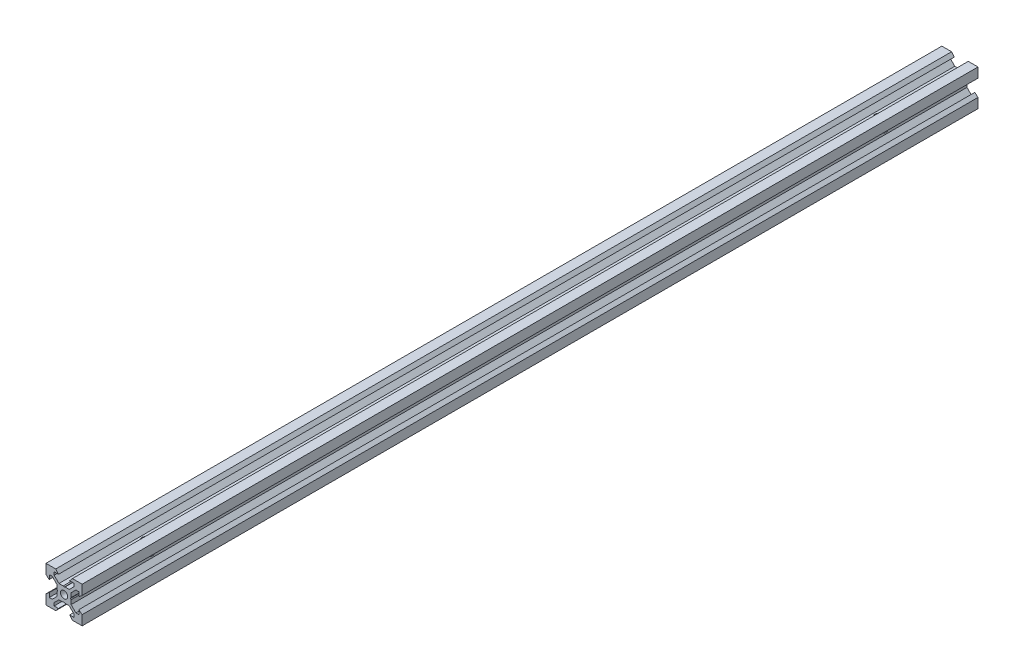
SolidWorks part; units mm, degrees
material "3.3535 (EN-AW 5754)"
ref_plane "Front Plane" through (0, 0, 0) normal (0, 0, 1) x (1, 0, 0)
ref_plane "Top Plane" through (0, 0, 0) normal (0, 1, 0) x (1, 0, 0)
ref_plane "Right Plane" through (0, 0, 0) normal (1, 0, 0) x (0, 0, -1)
sketch "Sketch1" plane through (0, 0, 0) normal (0, 0, 1) x (1, 0, 0)
  line L0 (10, 10) -> (4.6104, 10) construction
  line L1 (10, 10) -> (10, 4.6104) construction
  line L2 (10, -10) -> (10, -4.6104) construction
  line L3 (10, -10) -> (4.6104, -10) construction
  line L4 (10, 10) -> (10, 4.6104)
  line L5 (6.5607, 5.5) -> (8.2, 5.5)
  line L6 (5.5, 8.2) -> (5.5, 6.5607)
  line L7 (10, 10) -> (4.6104, 10)
  line L8 (10, 10) -> (10, 4.6104)
  line L9 (6.5607, 5.5) -> (3.9, 2.8393)
  line L10 (5.5, 6.5607) -> (2.8393, 3.9)
  line L11 (10, 4.6104) -> (8.2, 3.1)
  line L12 (4.6104, 10) -> (3.1, 8.2)
  line L13 (8.2, 3.1) -> (8.2, 5.5)
  line L14 (3.1, 8.2) -> (5.5, 8.2)
  line L15 (-6.5607, 5.5) -> (-8.2, 5.5)
  line L16 (6.5607, -5.5) -> (8.2, -5.5)
  line L17 (3.1, -8.2) -> (5.5, -8.2)
  line L18 (8.2, -3.1) -> (8.2, -5.5)
  line L19 (4.6104, -10) -> (3.1, -8.2)
  line L20 (10, -4.6104) -> (8.2, -3.1)
  line L21 (0.5196, -3.9) -> (0, -3.6)
  line L22 (0.5196, 3.9) -> (0, 3.6)
  line L23 (3.6, 0) -> (3.9, -0.5196)
  line L24 (3.9, 0.5196) -> (3.6, 0)
  line L25 (3.9, 0.5196) -> (3.9, 2.8393)
  line L26 (2.8393, 3.9) -> (0.5196, 3.9)
  line L27 (3.9, -2.8393) -> (3.9, -0.5196)
  line L28 (2.8393, -3.9) -> (0.5196, -3.9)
  line L29 (5.5, -6.5607) -> (2.8393, -3.9)
  line L30 (6.5607, -5.5) -> (3.9, -2.8393)
  line L31 (10, -10) -> (10, -4.6104)
  line L32 (10, -10) -> (4.6104, -10)
  line L33 (5.5, -8.2) -> (5.5, -6.5607)
  line L34 (-6.5607, -5.5) -> (-8.2, -5.5)
  line L35 (10, -10) -> (10, -4.6104)
  line L36 (0, 0) -> (0, 8.2) construction
  line L37 (-10, -10) -> (-4.6104, -10) construction
  line L38 (-10, -10) -> (-10, -4.6104) construction
  line L39 (-10, 10) -> (-10, 4.6104) construction
  line L40 (-10, 10) -> (-4.6104, 10) construction
  line L41 (-10, -10) -> (-10, -4.6104)
  line L43 (-5.5, -8.2) -> (-5.5, -6.5607)
  line L44 (-10, -10) -> (-4.6104, -10)
  line L45 (-10, -10) -> (-10, -4.6104)
  line L46 (-6.5607, -5.5) -> (-3.9, -2.8393)
  line L47 (-5.5, -6.5607) -> (-2.8393, -3.9)
  line L48 (-2.8393, -3.9) -> (-0.5196, -3.9)
  line L49 (-3.9, -2.8393) -> (-3.9, -0.5196)
  line L50 (-2.8393, 3.9) -> (-0.5196, 3.9)
  line L51 (-3.9, 0.5196) -> (-3.9, 2.8393)
  line L52 (-3.9, 0.5196) -> (-3.6, 0)
  line L53 (-3.6, 0) -> (-3.9, -0.5196)
  line L54 (-0.5196, 3.9) -> (0, 3.6)
  line L55 (-0.5196, -3.9) -> (0, -3.6)
  line L56 (-10, -4.6104) -> (-8.2, -3.1)
  line L57 (-4.6104, -10) -> (-3.1, -8.2)
  line L58 (-8.2, -3.1) -> (-8.2, -5.5)
  line L59 (-3.1, -8.2) -> (-5.5, -8.2)
  line L60 (-10, -10) -> (10, -10) construction
  line L61 (-10, -10) -> (-10, 10) construction
  line L62 (-3.1, 8.2) -> (-5.5, 8.2)
  line L63 (-8.2, 3.1) -> (-8.2, 5.5)
  line L64 (-4.6104, 10) -> (-3.1, 8.2)
  line L65 (-10, 4.6104) -> (-8.2, 3.1)
  line L66 (-5.5, 6.5607) -> (-2.8393, 3.9)
  line L67 (-6.5607, 5.5) -> (-3.9, 2.8393)
  line L68 (-10, 10) -> (-10, 4.6104)
  line L69 (-10, 10) -> (-4.6104, 10)
  line L70 (-5.5, 8.2) -> (-5.5, 6.5607)
  line L71 (-10, 10) -> (10, 10) construction
  line L72 (-10, 10) -> (-10, 4.6104)
  line L73 (10, -10) -> (10, 10) construction
  line L74 (-10, -10) -> (10, 10) construction
  line L75 (-10, 10) -> (10, -10) construction
  circle A0 centre (0, 0) radius 2
  dimension "D7" = 4
  dimension "D1" = 20
  dimension "D2" = 5.3896
  dimension "D3" = 4.5
  dimension "D4" = 50
  dimension "D5" = 1.8
  dimension "D6" = 1.5104
  dimension "D8" = 5.5
  dimension "D9" = 120
  dimension "D10" = 0.3
  dimension "D11" = 2.3197
  dimension "D12" = 7.8
  dimension "D13" = 7.8
  dimension "D14" = 1.5
  dimension "D15" = 2.6607
extrude "Boss-Extrude1" add sketch "Sketch1" along normal blind 496 contours L70 L62 L64 L69 L68 L65 L63 L15 L67 L51 L52 L53 L49 L46 L34 L58 L56 L41 L44 L57 L59 L43 L47 L48 L55 L21 L28 L29 L33 L17 L19 L32 L31 L20 L18 L16 L30 L27 L23 L24 L25 L9 L5 L13 L11 L4 L7 L12 L14 L6 L10 region at (9.7172, 7.3052, 0)
sketch "Sketch2" plane through (0, -3.9, 0) normal (0, -1, 0) x (-1, 0, 0)
  line L0 (0, -496) -> (0, -451) construction
  line L1 (0, -496) -> (0, 0) construction
  line L2 (0, 0) -> (0, -45) construction
  circle A0 centre (0, -451) radius 2
  circle A1 centre (0, -45) radius 2
  dimension "D2" = 4
  dimension "D4" = 4
  dimension "D1" = 45
  dimension "D3" = 45
extrude "Cut-Extrude1" cut sketch "Sketch2" against normal through all both and the other way through all
sketch "Sketch3" plane through (3.9, 0, 0) normal (1, 0, 0) x (0, 0, -1)
  line L0 (0, 0) -> (-45, 0) construction
  line L1 (-496, 0) -> (0, 0) construction
  line L2 (-496, 0) -> (-451, 0) construction
  circle A0 centre (-45, 0) radius 2
  circle A1 centre (-451, 0) radius 2
  dimension "D2" = 4
  dimension "D4" = 4
  dimension "D1" = 45
  dimension "D3" = 45
extrude "Cut-Extrude2" cut sketch "Sketch3" against normal through all both
